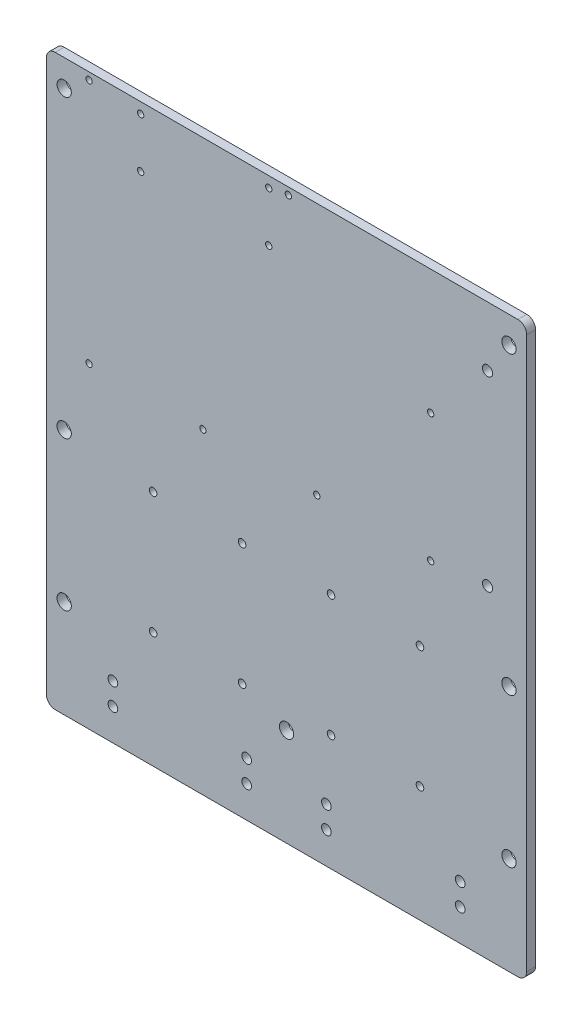
SolidWorks part; units mm, degrees
material "6061-T6 (SS)"
ref_plane "Front" through (0, 0, 0) normal (0, 0, 1) x (1, 0, 0)
ref_plane "Top" through (0, 0, 0) normal (0, 1, 0) x (1, 0, 0)
ref_plane "Right" through (0, 0, 0) normal (1, 0, 0) x (0, 0, -1)
sketch "Sketch1" plane through (0, 0, 0) normal (0, 0, 1) x (1, 0, 0)
  line L1 (-85.725, 101.6) -> (85.725, 101.6)
  line L2 (-85.725, 101.6) -> (-85.725, -101.6)
  line L3 (-85.725, -101.6) -> (85.725, -101.6)
  line L4 (85.725, 101.6) -> (85.725, -101.6)
  line L5 (-85.725, 101.6) -> (85.725, -101.6) construction
  line L6 (-85.725, -101.6) -> (85.725, 101.6) construction
  point P0 (0, 0)
  dimension "D1" = 171.45
  dimension "D2" = 203.2
extrude "Boss-Extrude1" add sketch "Sketch1" along normal blind 3.175
hole_wizard "#10 Clearance Hole1" positions "Sketch2" profile "Sketch3" hole size "#10" standard "ANSI Inch" end condition through all
sketch "Sketch2" plane through (0, 0, 3.175) normal (0, 0, 1) x (1, 0, 0)
  point P0 (-79.375, 92.075)
  point P2 (79.375, 92.075)
  point P4 (79.375, -66.675)
  point P6 (-79.375, -66.675)
  point P8 (-79.375, -13.462)
  point P10 (79.375, -13.462)
  point P37 (0, -66.675)
  point P45 (0, 0)
  point P49 (0, 0)
sketch "Sketch3" plane through (-79.375, 92.075, 3.175) normal (1, 0, 0) x (0, -1, 0)
  line L0 (0, 0) -> (0, 3.175)
  line L1 (0, 3.175) -> (2.5527, 3.175)
  line L2 (2.5527, 3.175) -> (2.5527, 0)
  line L3 (2.5527, 0) -> (0, 0)
  line L4 (0, -6.35) -> (0, 107.95) construction
  dimension "Thru Hole Dia." = 5.1054
  dimension "Thru Hole Depth" = 3.175
hole_wizard "#6-32 Tapped Hole1" positions "Sketch4" profile "Sketch5" tap size "#6-32" standard "ANSI Inch" end condition through all
sketch "Sketch4" plane through (0, 0, 3.175) normal (0, 0, 1) x (1, 0, 0)
  point P0 (-47.625, -60.2)
  point P2 (-47.625, -16.8)
sketch "Sketch5" plane through (-47.625, -60.2, 3.175) normal (1, 0, 0) x (0, -1, 0)
  line L0 (0, 0) -> (0, 3.175)
  line L1 (0, 3.175) -> (1.3525, 3.175)
  line L2 (1.3525, 3.175) -> (1.3525, 0)
  line L3 (1.3525, 0) -> (0, 0)
  line L4 (0, -6.35) -> (0, 107.95) construction
  dimension "Thru Tap Drill Dia." = 2.7051
  dimension "Thru Tap Drill Depth" = 3.175
cosmetic thread "Hole Thread1" parameters "D2"=3.5052
cosmetic thread "Hole Thread2" parameters "D2"=3.5052
pattern_linear "LPattern1" count 4 spacing 31.75 along (1, 0, 0) of "#6-32 Tapped Hole1"
cosmetic thread "Hole Thread3" parameters "D2"=3.5052
cosmetic thread "Hole Thread4" parameters "D2"=3.5052
cosmetic thread "Hole Thread5" parameters "D2"=3.5052
cosmetic thread "Hole Thread6" parameters "D2"=3.5052
cosmetic thread "Hole Thread7" parameters "D2"=3.5052
cosmetic thread "Hole Thread8" parameters "D2"=3.5052
hole_wizard "#8-32 Tapped Hole1" positions "Sketch6" profile "Sketch7" tap size "#8-32" standard "ANSI Inch" end condition through all
sketch "Sketch6" plane through (0, 0, 3.175) normal (0, 0, 1) x (1, 0, 0)
  point P0 (-61.976, -82.423)
  point P2 (-61.976, -90.297)
  point P4 (-14.224, -82.423)
  point P6 (-14.224, -90.297)
sketch "Sketch7" plane through (-61.976, -82.423, 3.175) normal (1, 0, 0) x (0, -1, 0)
  line L0 (0, 0) -> (0, 3.175)
  line L1 (0, 3.175) -> (1.7272, 3.175)
  line L2 (1.7272, 3.175) -> (1.7272, 0)
  line L3 (1.7272, 0) -> (0, 0)
  line L4 (0, -6.35) -> (0, 107.95) construction
  dimension "Thru Tap Drill Dia." = 3.4544
  dimension "Thru Tap Drill Depth" = 3.175
cosmetic thread "Hole Thread9" parameters "D2"=4.1656
cosmetic thread "Hole Thread10" parameters "D2"=4.1656
cosmetic thread "Hole Thread11" parameters "D2"=4.1656
cosmetic thread "Hole Thread12" parameters "D2"=4.1656
mirror "Mirror1" about plane through (0, 0, 0) normal (1, 0, 0) of "#8-32 Tapped Hole1"
cosmetic thread "Hole Thread13" parameters "D2"=4.1656
cosmetic thread "Hole Thread14" parameters "D2"=4.1656
cosmetic thread "Hole Thread15" parameters "D2"=4.1656
cosmetic thread "Hole Thread16" parameters "D2"=4.1656
hole_wizard "M3 Clearance Hole1" positions "Sketch8" profile "Sketch9" hole size "M3" standard "ANSI Metric" end condition through all
sketch "Sketch8" plane through (0, 0, 0) normal (0, 0, -1) x (-1, 0, 0)
  point P0 (-71.725, 80.3338)
  point P2 (-71.725, 13.8338)
sketch "Sketch9" plane through (71.725, 80.3338, 0) normal (1, 0, 0) x (0, 1, 0)
  line L0 (0, 0) -> (0, 3.175)
  line L1 (0, 3.175) -> (1.8, 3.175)
  line L2 (1.8, 3.175) -> (1.8, 0)
  line L3 (1.8, 0) -> (0, 0)
  line L4 (0, -6.35) -> (0, 107.95) construction
  dimension "Thru Hole Dia." = 3.6
  dimension "Thru Hole Depth" = 3.175
fillet "Fillet1" radius 3.175 4 edges at (-85.725, -101.6, 1.5875) (-85.725, 101.6, 1.5875) (85.725, 101.6, 1.5875) (85.725, -101.6, 1.5875)
hole_wizard "#4-40 Tapped Hole1" positions "Sketch10" profile "Sketch11" tap size "#4-40" standard "ANSI Inch" end condition through all
sketch "Sketch10" plane through (0, 0, 3.175) normal (0, 0, 1) x (1, 0, 0)
  point P0 (-70.485, 99.06)
  point P2 (-52.07, 80.01)
  point P4 (-52.07, 97.79)
  point P6 (-6.35, 97.79)
  point P8 (0.635, 99.06)
  point P10 (-6.35, 80.01)
  point P12 (-70.485, 11.43)
  point P14 (-29.845, 11.43)
  point P16 (10.795, 11.43)
  point P18 (51.435, 11.43)
  point P20 (51.435, 57.15)
  point P29 (0, 0)
  point P36 (0, 0)
  point P39 (0, 0)
  point P42 (0, 0)
  point P45 (0, 0)
  point P48 (0, 0)
sketch "Sketch11" plane through (-70.485, 99.06, 3.175) normal (1, 0, 0) x (0, -1, 0)
  line L0 (0, 0) -> (0, 3.175)
  line L1 (0, 3.175) -> (1.1303, 3.175)
  line L2 (1.1303, 3.175) -> (1.1303, 0)
  line L3 (1.1303, 0) -> (0, 0)
  line L4 (0, -6.35) -> (0, 107.95) construction
  dimension "Thru Tap Drill Dia." = 2.2606
  dimension "Thru Tap Drill Depth" = 3.175
cosmetic thread "Hole Thread17" parameters "D2"=2.8448
cosmetic thread "Hole Thread18" parameters "D2"=2.8448
cosmetic thread "Hole Thread19" parameters "D2"=2.8448
cosmetic thread "Hole Thread20" parameters "D2"=2.8448
cosmetic thread "Hole Thread21" parameters "D2"=2.8448
cosmetic thread "Hole Thread22" parameters "D2"=2.8448
cosmetic thread "Hole Thread23" parameters "D2"=2.8448
cosmetic thread "Hole Thread24" parameters "D2"=2.8448
cosmetic thread "Hole Thread25" parameters "D2"=2.8448
cosmetic thread "Hole Thread26" parameters "D2"=2.8448
cosmetic thread "Hole Thread27" parameters "D2"=2.8448
